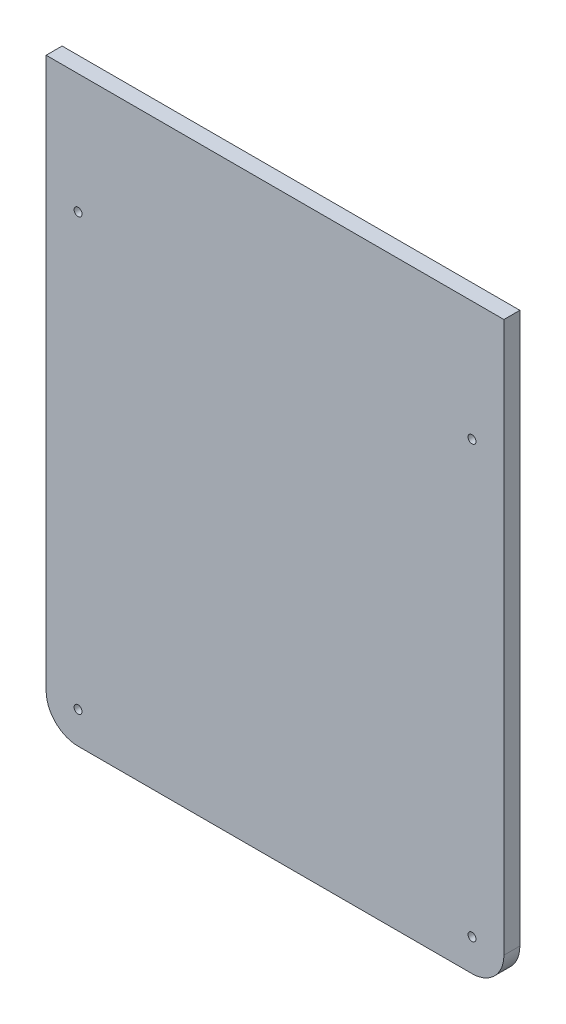
SolidWorks part; units mm, degrees
material "Beech"
ref_plane "Front Plane" through (0, 0, 0) normal (0, 0, 1) x (1, 0, 0)
ref_plane "Top Plane" through (0, 0, 0) normal (0, 1, 0) x (1, 0, 0)
ref_plane "Right Plane" through (0, 0, 0) normal (1, 0, 0) x (0, 0, -1)
sketch "Sketch1" plane through (0, 0, 0) normal (0, 0, 1) x (1, 0, 0)
  line L0 (-19.05, 903.0272) -> (-19.05, 155.124) construction
  line L1 (163.1, 903.0272) -> (163.1, 155.124) construction
  line L2 (-19.05, 903.0272) -> (163.1, 903.0272)
  line L3 (0, 903.0272) -> (19.05, 903.0272) construction
  line L4 (-6.35, 671.2522) -> (150.4, 671.2522) construction
  line L5 (163.1, 683.9522) -> (163.1, 855.4022) construction
  line L6 (-6.35, 671.2522) -> (150.4, 671.2522)
  line L7 (163.1, 683.9522) -> (163.1, 903.0272)
  line L10 (-19.05, 903.0272) -> (-19.05, 683.9522)
  arc A0 (-19.05, 683.9522) -> (-6.35, 671.2522) centre (-6.35, 683.9522) ccw construction
  arc A1 (150.4, 671.2522) -> (163.1, 683.9522) centre (150.4, 683.9522) ccw construction
  arc A2 (-19.05, 683.9522) -> (-6.35, 671.2522) centre (-6.35, 683.9522) ccw
  arc A3 (150.4, 671.2522) -> (163.1, 683.9522) centre (150.4, 683.9522) ccw
extrude "Boss-Extrude1" add sketch "Sketch1" along normal blind 6.35
hole_wizard "Hole1" positions "Sketch2" profile "Sketch3" legacy
sketch "Sketch2" plane through (72.025, -454.7856, 19.05) normal (0, 0, 1) x (1, 0, 0)
  point P0 (-78.375, 1310.1878)
  point P3 (-78.375, 1138.7378)
  point P6 (78.375, 1138.7378)
  point P9 (78.375, 1310.1878)
sketch "Sketch3" plane through (-6.35, 855.4022, 19.05) normal (1, 0, 0) x (0, -1, 0)
  line L0 (0, 0) -> (0, 32.7039)
  line L1 (0, 32.7039) -> (1.5875, 31.75)
  line L2 (1.5875, 31.75) -> (1.5875, 4.0177)
  line L3 (1.5875, 4.0177) -> (5.08, 0)
  line L4 (5.08, 0) -> (0, 0)
  line L5 (0, -14.3089) -> (0, 102.4216) construction
  line L6 (0, 32.7039) -> (-1.5875, 31.75) construction
  line L7 (-1.5875, 4.0177) -> (-5.08, 0) construction
  dimension "Diameter" = 3.175
  dimension "Depth" = 31.75
  dimension "C-Sink Diameter" = 10.16
  dimension "C-Sink Angle" = 82
  dimension "Drill Angle" = 118
